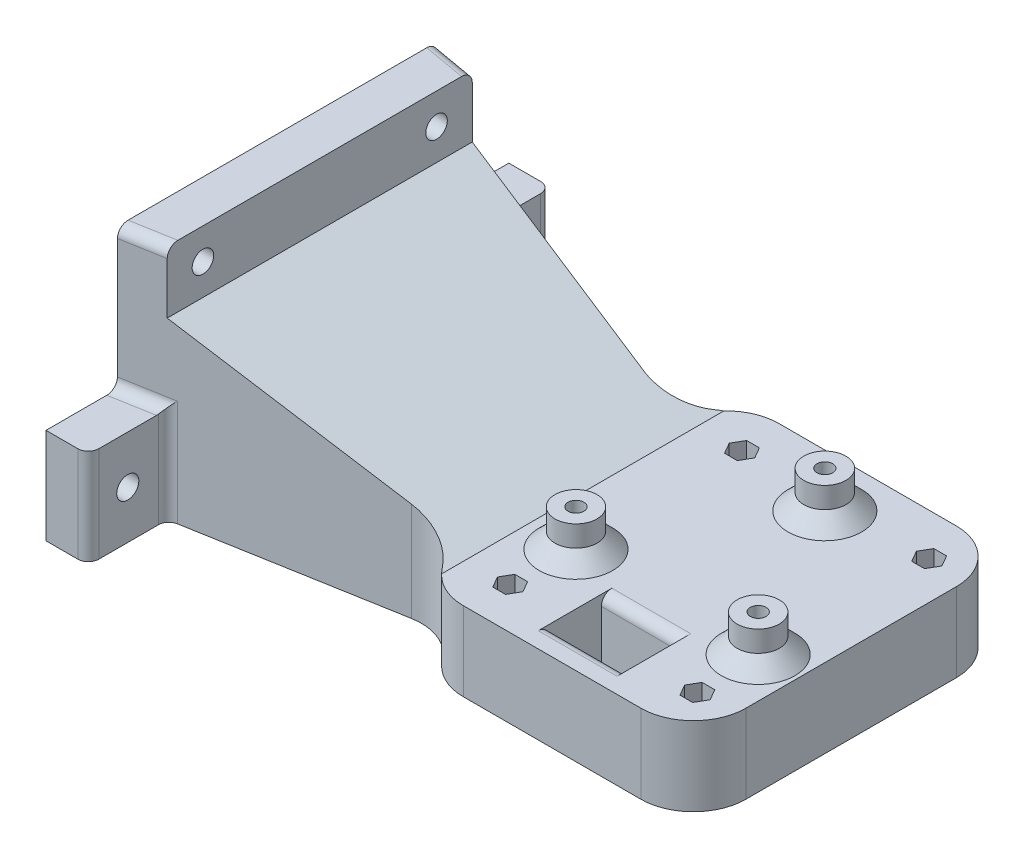
SolidWorks part; units mm, degrees
ref_plane "前视基准面" through (0, 0, 0) normal (0, 0, 1) x (1, 0, 0)
ref_plane "上视基准面" through (0, 0, 0) normal (0, 1, 0) x (1, 0, 0)
ref_plane "右视基准面" through (0, 0, 0) normal (1, 0, 0) x (0, 0, -1)
sketch "草图1" plane through (0, 0, 0) normal (0, 1, 0) x (1, 0, 0)
  line L0 (-25, 0) -> (25, 0) construction
  line L1 (-25, 30) -> (25, 30)
  line L2 (-25, 30) -> (-25, -30)
  line L3 (-25, -30) -> (25, -30)
  line L4 (25, 30) -> (25, -30)
  line L5 (-25, 30) -> (25, -30) construction
  line L6 (-25, -30) -> (25, 30) construction
  line L7 (0, 30) -> (0, -30) construction
  line L8 (0, 0) -> (-17.3205, -10) construction
  line L9 (0, 0) -> (0, 20) construction
  line L10 (0, 0) -> (17.3205, -10) construction
  circle A0 centre (-17.7955, 22.0345) radius 1
  circle A1 centre (17.7955, 22.0345) radius 1
  circle A2 centre (17.7955, -22.0345) radius 1
  circle A3 centre (-17.7955, -22.0345) radius 1
  circle A8 centre (0, 0) radius 20 construction
  circle A9 centre (-17.3205, -10) radius 1.5
  circle A10 centre (17.3205, -10) radius 1.5
  circle A11 centre (0, 20) radius 1.5
  point P0 (0, 0)
  dimension "D4" = 2
  dimension "D5" = 2
  dimension "D14" = 40
  dimension "D15" = 3
  dimension "D16" = 3
  dimension "D17" = 3
  dimension "D1" = 60
  dimension "D2" = 50
  dimension "D3" = 35.591
  dimension "D6" = 7.2045
  dimension "D7" = 7.9655
extrude "凸台-拉伸1" add sketch "草图1" along normal blind 5 and the other way blind 10
fillet "圆角1" radius 10 1 edges at (25, -2.5, -30)
sketch "草图5" plane through (0, 5, 0) normal (0, 1, 0) x (1, 0, 0)
  circle A1 centre (-17.3205, -10) radius 4
  circle A2 centre (17.3205, -10) radius 4
  circle A3 centre (0, 20) radius 4
  circle A4 centre (-17.3205, -10) radius 1.5
  circle A5 centre (17.3205, -10) radius 1.5
  circle A6 centre (0, 20) radius 1.5
  dimension "D1" = 8
  dimension "D2" = 8
  dimension "D3" = 8
extrude "凸台-拉伸3" add sketch "草图5" along normal blind 7
sketch "草图6" plane through (0, -10, 0) normal (0, -1, 0) x (1, 0, 0)
  circle A0 centre (-17.3205, 10) radius 3.5
  circle A1 centre (17.3205, 10) radius 3.5
  circle A2 centre (0, -20) radius 3.5
  dimension "D1" = 7
  dimension "D2" = 7
  dimension "D3" = 7
extrude "切除-拉伸1" cut sketch "草图6" against normal blind 6
sketch "草图7" plane through (0, 5, 0) normal (0, 1, 0) x (1, 0, 0)
  line L0 (0, 0) -> (0, -30) construction
  line L1 (-25, -30) -> (25, -30) construction
  line L3 (0, 0) -> (0, -15) construction
  line L4 (-7.5, -15) -> (7.5, -15)
  line L5 (-7.5, -15) -> (-7.5, -25)
  line L6 (-7.5, -25) -> (7.5, -25)
  line L7 (7.5, -15) -> (7.5, -25)
  line L8 (-7.5, -15) -> (7.5, -25) construction
  line L9 (-7.5, -25) -> (7.5, -15) construction
  point P9 (0, -20)
  dimension "D1" = 10
  dimension "D2" = 15
  dimension "D3" = 15
extrude "切除-拉伸2" cut sketch "草图7" against normal through all
sketch "草图9" plane through (0, 5, 0) normal (0, 1, 0) x (1, 0, 0)
  line L1 (-15.3706, 22.0345) -> (-16.5831, 24.1345)
  line L2 (-16.5831, 24.1345) -> (-19.0079, 24.1345)
  line L3 (-19.0079, 24.1345) -> (-20.2204, 22.0345)
  line L4 (-20.2204, 22.0345) -> (-19.0079, 19.9345)
  line L5 (-19.0079, 19.9345) -> (-16.5831, 19.9345)
  line L6 (-16.5831, 19.9345) -> (-15.3706, 22.0345)
  line L7 (20.2204, 22.0345) -> (19.0079, 24.1345)
  line L8 (19.0079, 24.1345) -> (16.5831, 24.1345)
  line L9 (16.5831, 24.1345) -> (15.3706, 22.0345)
  line L10 (15.3706, 22.0345) -> (16.5831, 19.9345)
  line L11 (16.5831, 19.9345) -> (19.0079, 19.9345)
  line L12 (19.0079, 19.9345) -> (20.2204, 22.0345)
  line L13 (20.2204, -22.0345) -> (19.0079, -19.9345)
  line L14 (19.0079, -19.9345) -> (16.5831, -19.9345)
  line L15 (16.5831, -19.9345) -> (15.3706, -22.0345)
  line L16 (15.3706, -22.0345) -> (16.5831, -24.1345)
  line L17 (16.5831, -24.1345) -> (19.0079, -24.1345)
  line L18 (19.0079, -24.1345) -> (20.2204, -22.0345)
  line L19 (-15.3706, -22.0345) -> (-16.5831, -19.9345)
  line L20 (-16.5831, -19.9345) -> (-19.0079, -19.9345)
  line L21 (-19.0079, -19.9345) -> (-20.2204, -22.0345)
  line L22 (-20.2204, -22.0345) -> (-19.0079, -24.1345)
  line L23 (-19.0079, -24.1345) -> (-16.5831, -24.1345)
  line L24 (-16.5831, -24.1345) -> (-15.3706, -22.0345)
  circle A0 centre (-17.7955, 22.0345) radius 2.1 construction
  circle A1 centre (17.7955, 22.0345) radius 2.1 construction
  circle A2 centre (17.7955, -22.0345) radius 2.1 construction
  circle A3 centre (-17.7955, -22.0345) radius 2.1 construction
  point P28 (-17.7955, -19.9345)
  dimension "D1" = 4.2
  dimension "D2" = 4.2
  dimension "D3" = 4.2
  dimension "D4" = 4.2
extrude "切除-拉伸3" cut sketch "草图9" against normal blind 10
chamfer "倒角1" distance 3 angle 45 3 edges at (0, 5, -16) (17.3205, 5, 14) (-17.3205, 5, 14)
fillet "圆角6" radius 10 1 edges at (25, -2.5, 30)
sketch "草图13" plane through (0, 5, 0) normal (0, 1, 0) x (1, 0, 0)
  line L0 (-25, 20) -> (-84.0885, 30.4189)
  line L1 (-84.0885, 30.4189) -> (-84.0885, -30.4189)
  line L2 (-84.0885, -30.4189) -> (-25, -20)
  line L3 (-25, -20) -> (-25, 20)
  dimension "D1" = 100
  dimension "D2" = 100
  dimension "D3" = 60
  dimension "D4" = 60
extrude "凸台-拉伸7" add sketch "草图13" against normal up to surface (15 mm away) up to face at (0, -10, 20)
sketch "草图15" plane through (0, 5, 0) normal (0, 1, 0) x (1, 0, 0)
  line L0 (-84.0885, 30.4189) -> (-84.0885, -30.4189)
  line L1 (-84.0885, -30.4189) -> (-76.0415, -29)
  line L2 (-84.0885, -30.4189) -> (-25, -20) construction
  line L3 (-76.0415, -29) -> (-76.0415, 29)
  line L4 (-25, 20) -> (-84.0885, 30.4189) construction
  line L5 (-76.0415, 29) -> (-84.0885, 30.4189)
  dimension "D1" = 58
extrude "凸台-拉伸8" add sketch "草图15" along normal blind 30
chamfer "倒角2" distance 50 angle 20 1 edges at (-76.0415, 5, 0) first distance on face at (0, 5, -13)
sketch "草图16" plane through (-76.0415, 0, 0) normal (1, 0, 0) x (0, 0, -1)
  line L0 (-29, 35) -> (-15.4202, 23.1985) construction
  line L1 (-29, 23.1985) -> (29, 23.1985) construction
  line L2 (-29, 23.1985) -> (-15.4202, 35) construction
  line L3 (-29, 35) -> (29, 35) construction
  line L4 (0, 23.1985) -> (0, 35) construction
  circle A0 centre (-22.2101, 29.0993) radius 2.05
  circle A1 centre (22.2101, 29.0993) radius 2.05
  dimension "D1" = 4.1
extrude "切除-拉伸4" cut sketch "草图16" against normal blind 30
fillet "圆角7" radius 10 2 edges at (-25, -2.5, 20) (-25, -2.5, -20)
fillet "圆角8" radius 10 2 edges at (-25, -2.5, 30) (-25, -2.5, -30)
sketch "草图17" plane through (-76.0415, 0, 0) normal (1, 0, 0) x (0, 0, -1)
  line L0 (-29, 23.1985) -> (-29, 8.1985) construction
  line L1 (-29, 8.1985) -> (-44, 8.1985)
  line L2 (-44, 8.1985) -> (-44, -10)
  line L3 (-44, -10) -> (-29, -10)
  line L4 (-29, -10) -> (-29, 8.1985)
  line L5 (0, 0) -> (0, 17.857) construction
  line L10 (-44, 8.1985) -> (-29, -10) construction
  line L11 (-44, -10) -> (-29, 8.1985) construction
  line L16 (-30, -10) -> (-20, -10) construction
  line L17 (44, -10) -> (29, -10)
  line L18 (44, 8.1985) -> (44, -10)
  line L19 (29, 8.1985) -> (44, 8.1985)
  line L20 (29, -10) -> (29, 8.1985)
  circle A0 centre (-36.5, -0.9007) radius 2.1
  circle A1 centre (36.5, -0.9007) radius 2.1
  dimension "D4" = 4.2
  dimension "D1" = 15
  dimension "D2" = 15
extrude "凸台-拉伸9" add sketch "草图17" against normal up to surface (8.0469 mm away) up to face at (-84.0885, 29.0993, 24.2601)
fillet "圆角9" radius 2 8 edges at (-80.065, 8.1985, -29.7094) (-80.065, 8.1985, 29.7094) (-76.0415, -0.9007, -44) (-76.0415, -0.9007, 44) (-80.065, 35, 29.7094) (-80.065, 35, -29.7094) (-76.0415, -0.9007, 29) (-76.0415, -0.9007, -29)
fillet "圆角10" radius 2 4 edges at (0, -10, 25) (0, -10, 15) (0, 5, 25) (0, 5, 15)
